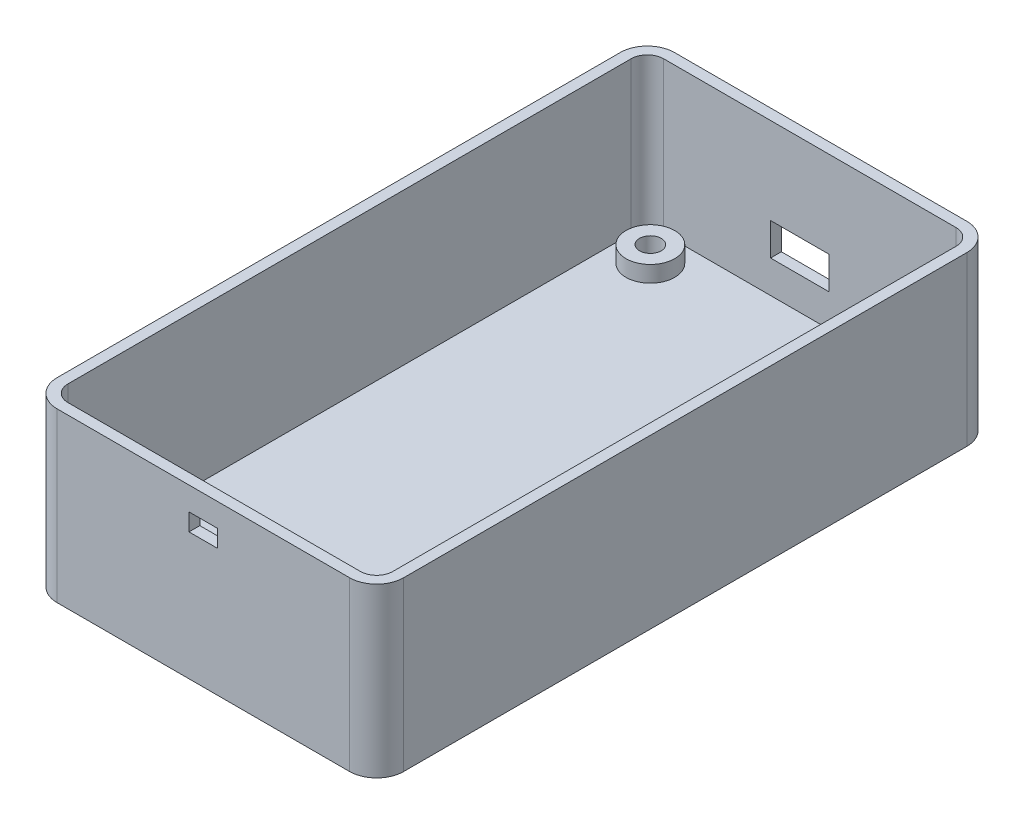
SolidWorks part; units mm, degrees
ref_plane "Front Plane" through (0, 0, 0) normal (0, 0, 1) x (1, 0, 0)
ref_plane "Top Plane" through (0, 0, 0) normal (0, 1, 0) x (1, 0, 0)
ref_plane "Right Plane" through (0, 0, 0) normal (1, 0, 0) x (0, 0, -1)
sketch "Sketch1" plane through (0, 0, 0) normal (0, 1, 0) x (1, 0, 0)
  line L0 (0, 0) -> (0, 19.2016) construction
  line L1 (-25.3206, 52.85) -> (25.3206, 52.85) construction
  line L2 (-25.3206, 52.85) -> (-25.3206, -52.85) construction
  line L3 (-25.3206, -52.85) -> (25.3206, -52.85) construction
  line L4 (25.3206, 52.85) -> (25.3206, -52.85) construction
  line L5 (-25.3206, 52.85) -> (25.3206, -52.85) construction
  line L6 (-25.3206, -52.85) -> (25.3206, 52.85) construction
  line L7 (21.5, 49.05) -> (-21.5, 49.05) construction
  line L8 (-23.5, 51.05) -> (23.5, 51.05) construction
  line L9 (0, 0) -> (38.1053, 0) construction
  line L10 (-23.5, 47.05) -> (-23.5, -47.05) construction
  line L12 (27, 55) -> (-27, 55)
  line L13 (30, 52) -> (30, -52)
  line L14 (27, -55) -> (-27, -55)
  line L15 (-30, 52) -> (-30, -52)
  line L16 (30, 55) -> (-30, -55) construction
  line L17 (30, -55) -> (-30, 55) construction
  circle A0 centre (-23.5, 49.05) radius 2
  circle A1 centre (23.5, 49.05) radius 2
  circle A2 centre (23.5, -49.05) radius 2
  circle A3 centre (-23.5, -49.05) radius 2
  circle A4 centre (-23.5, 49.05) radius 4.5
  circle A5 centre (23.5, 49.05) radius 4.5
  circle A6 centre (-23.5, -49.05) radius 4.5
  circle A7 centre (23.5, -49.05) radius 4.5
  arc A8 (27, 55) -> (30, 52) centre (27, 52) cw
  arc A9 (30, -52) -> (27, -55) centre (27, -52) cw
  arc A10 (-30, -52) -> (-27, -55) centre (-27, -52) ccw
  arc A11 (-30, 52) -> (-27, 55) centre (-27, 52) cw
  point P0 (0, 0)
  dimension "D1" = 43
  dimension "D3" = 4
  dimension "D8" = 3
  dimension "D2" = 1.8
  dimension "D4" = 94.1
  dimension "D6" = 110
  dimension "D7" = 60
  dimension "D5" = 2.5
extrude "Boss-Extrude1" add sketch "Sketch1" against normal blind 3 contours A0 | L14 A10 L15 A11 L12 A8 L13 A9 | A3 | A1 | A2 region at (-23.5, 0, -49.05)
extrude "Boss-Extrude2" add sketch "Sketch1<3>" along normal blind 3 contours A4 A0 | A5 A1 | A7 A2 | A6 | A3 region at (-27.8727, 0, -49.05) region at (19.1273, 0, -49.05) region at (19.1273, 0, 49.05)
sketch "Sketch1<3>" plane through (0, 0, 0) normal (0, 1, 0) x (1, 0, 0) same geometry as "Sketch1"
sketch "Sketch2" plane through (0, 0, 0) normal (0, 1, 0) x (1, 0, 0)
  line L12 (32, -52) -> (32, 52)
  line L13 (27, 57) -> (-27, 57)
  line L15 (-27, -57) -> (27, -57)
  line L20 (-32, 52) -> (-32, -52)
  line L21 (-27, -57) -> (27, -57)
  line L22 (32, -52) -> (32, 52)
  line L23 (27, 57) -> (-27, 57)
  line L24 (30, -52) -> (30, 52)
  line L25 (27, 55) -> (-27, 55)
  line L26 (-30, 52) -> (-30, -52)
  line L27 (-27, -55) -> (27, -55)
  line L28 (30, -52) -> (30, 52)
  line L29 (27, 55) -> (-27, 55)
  line L30 (-30, 52) -> (-30, -52)
  line L31 (-27, -55) -> (27, -55)
  arc A12 (27, -57) -> (32, -52) centre (27, -52) ccw
  arc A13 (32, 52) -> (27, 57) centre (27, 52) ccw
  arc A14 (-27, 57) -> (-32, 52) centre (-27, 52) ccw
  arc A15 (-32, -52) -> (-27, -57) centre (-27, -52) ccw
  arc A20 (-32, -52) -> (-27, -57) centre (-27, -52) ccw
  arc A21 (27, -57) -> (32, -52) centre (27, -52) ccw
  arc A22 (32, 52) -> (27, 57) centre (27, 52) ccw
  arc A23 (-27, 57) -> (-32, 52) centre (-27, 52) ccw
  arc A24 (27, -55) -> (30, -52) centre (27, -52) ccw
  arc A25 (30, 52) -> (27, 55) centre (27, 52) ccw
  arc A26 (-27, 55) -> (-30, 52) centre (-27, 52) ccw
  arc A27 (-30, -52) -> (-27, -55) centre (-27, -52) ccw
  arc A28 (27, -55) -> (30, -52) centre (27, -52) ccw
  arc A29 (30, 52) -> (27, 55) centre (27, 52) ccw
  arc A30 (-27, 55) -> (-30, 52) centre (-27, 52) ccw
  arc A31 (-30, -52) -> (-27, -55) centre (-27, -52) ccw
  dimension "D2" = 0
  dimension "D3" = 2
extrude "Boss-Extrude3" add sketch "Sketch2" along normal blind 28 and the other way up to surface (3 mm away) contours L20 A15 L15 A12 L12 A13 L13 A14 A31 L30 A30 L29 A29 L28 A28 L31 region at (29.6111, 0, 54.6111) other way up to face at (23.5, -3, 51.05)
chamfer "Chamfer1" distance 3.5 angle 30 4 edges at (-23.5, -3, 47.05) (23.5, -3, 51.05) (-23.5, -3, -47.05) (23.5, -3, -51.05) first distance on face at (23.5, -3, 51.05)
sketch "Sketch3" plane through (0, 0, -57) normal (0, 0, -1) x (-1, 0, 0)
  line L1 (-3.5, 12) -> (7.25, 12)
  line L2 (-3.5, 12) -> (-3.5, 6)
  line L3 (-3.5, 6) -> (7.25, 6)
  line L4 (7.25, 12) -> (7.25, 6)
  line L5 (-19, 3) -> (-28, 3) construction
  line L6 (0, 0) -> (0, 28) construction
  line L7 (-27, 28) -> (27, 28) construction
  line L8 (-28.5, 0) -> (28.5, 0) construction
  point P11 (0, -0.4746)
  point P14 (0, 0)
  point P15 (0, 0)
  point P16 (0, 0)
  dimension "D1" = 3
  dimension "D2" = 57
  dimension "D3" = 25
  dimension "D4" = 21.25
  dimension "D5" = 6
extrude "Cut-Extrude4" cut sketch "Sketch3" along normal mid plane 5
sketch "Sketch4" plane through (0, 0, 57) normal (0, 0, 1) x (1, 0, 0)
  line L0 (0, 0) -> (0, 33.5553) construction
  line L1 (-2.65, 23.7) -> (2.65, 23.7)
  line L2 (-2.65, 23.7) -> (-2.65, 20.5)
  line L3 (-2.65, 20.5) -> (2.65, 20.5)
  line L4 (2.65, 23.7) -> (2.65, 20.5)
  line L5 (27, 0) -> (-27, 0) construction
  line L6 (-19, 3) -> (-28, 3) construction
  point P10 (-3.0729, 20.5)
  dimension "D1" = 5.3
  dimension "D2" = 3.2
  dimension "D3" = 17.5
extrude "Cut-Extrude5" cut sketch "Sketch4" against normal mid plane 5
